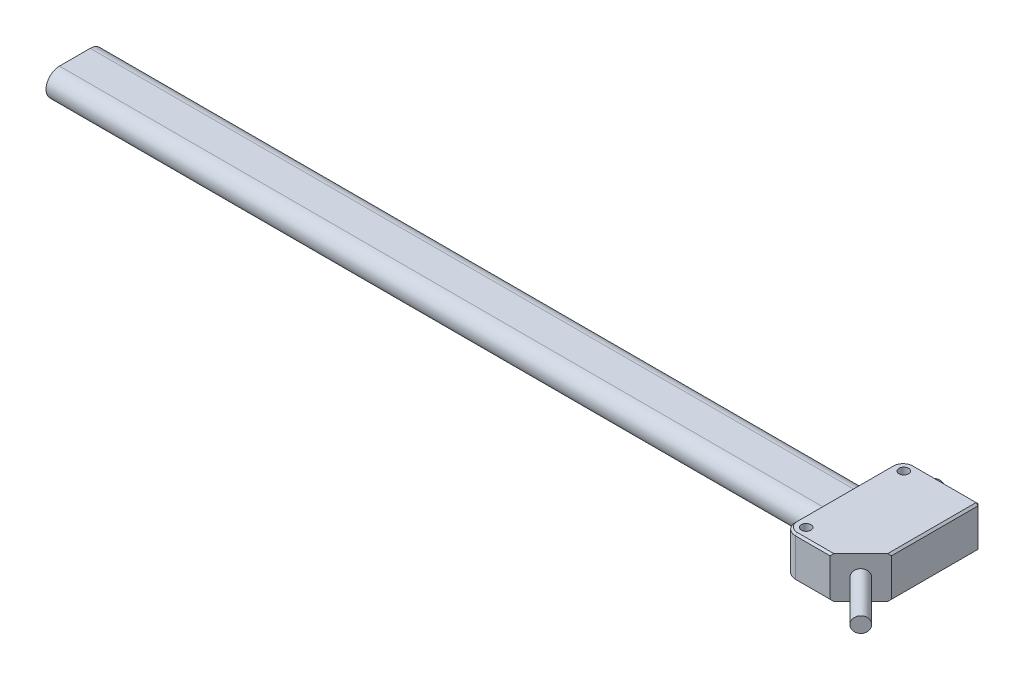
SolidWorks part; units mm, degrees
material "ABS PC"
ref_plane "前视基准面" through (0, 0, 0) normal (0, 0, 1) x (1, 0, 0)
ref_plane "上视基准面" through (0, 0, 0) normal (0, 1, 0) x (1, 0, 0)
ref_plane "右视基准面" through (0, 0, 0) normal (1, 0, 0) x (0, 0, -1)
sketch "草图1" plane through (0, 0, 0) normal (0, 1, 0) x (1, 0, 0)
  line L0 (20, -23) -> (12, -31)
  line L1 (0, 0) -> (20, 0)
  line L2 (0, 0) -> (0, -31)
  line L3 (0, -31) -> (12, -31)
  line L4 (20, 0) -> (20, -23)
  dimension "D1" = 31
  dimension "D2" = 20
  dimension "D3" = 8
  dimension "D4" = 135
extrude "凸台-拉伸1" add sketch "草图1" along normal mid plane 10.8
sketch "草图2" plane through (0, 0, 0) normal (0, 0, -1) x (-1, 0, 0)
  line L0 (-8.1, 2.3) -> (-8.1, -2.3) construction
  line L1 (-6, 2.3) -> (-6, -2.3)
  line L2 (-10.2, 2.3) -> (-10.2, -2.3)
  line L4 (0, 5.4) -> (0, -5.4) construction
  arc A0 (-6, 2.3) -> (-10.2, 2.3) centre (-8.1, 2.3) ccw
  arc A1 (-10.2, -2.3) -> (-6, -2.3) centre (-8.1, -2.3) ccw
  point P2 (-8.1, 0)
  point P11 (-8.1, 4.4)
  point P12 (-8.1, -4.4)
  dimension "D1" = 4.2
  dimension "D2" = 6
  dimension "D3" = 8.8
extrude "凸台-拉伸2" add sketch "草图2" along normal blind 2.1
fillet "圆角1" radius 2.1 4 edges at (6, 0, -2.1) (8.1, -4.4, -2.1) (10.2, 0, -2.1) (8.1, 4.4, -2.1)
sketch "草图3" plane through (0, 0, 0) normal (-1, 0, 0) x (0, 0, 1)
  line L0 (11.5, 0) -> (19.5, 0) construction
  line L1 (11.5, 3.5) -> (19.5, 3.5)
  line L2 (11.5, -3.5) -> (19.5, -3.5)
  line L3 (0, 5.4) -> (0, -5.4) construction
  arc A0 (11.5, 3.5) -> (11.5, -3.5) centre (11.5, 0) ccw
  arc A1 (19.5, -3.5) -> (19.5, 3.5) centre (19.5, 0) ccw
  point P3 (15.5, 0)
  dimension "D1" = 7
  dimension "D2" = 19.5
  dimension "D3" = 8
wrap "包覆1" sketch "草图3" wrap type scribe source sketch "草图3" face at (0, 0, 15.5)
hole_wizard "M3 螺纹孔1" positions "草图4" profile "草图5" tap size "M3" standard "GB" end condition through all
sketch "草图4" plane through (0, 5.4, 0) normal (0, 1, 0) x (1, 0, 0)
  line L0 (20, 0) -> (0, 0) construction
  line L1 (0, 0) -> (0, -31) construction
  point P0 (3, -2.8)
  point P2 (3, -28.2)
  dimension "D1" = 25.4
  dimension "D2" = 2.8
  dimension "D3" = 3
sketch "草图5" plane through (3, 5.4, 2.8) normal (1, 0, 0) x (0, 0, 1)
  line L0 (0, 0) -> (0, 10.8)
  line L1 (0, 10.8) -> (1.25, 10.8)
  line L2 (1.25, 10.8) -> (1.25, 0)
  line L5 (1.25, 0) -> (0, 0)
  line L11 (0, -6.35) -> (0, 107.95) construction
  dimension "通孔螺纹孔钻头直径" = 2.5
  dimension "通孔螺纹孔钻头深度" = 10.8
cosmetic thread "孔螺蚊线1" parameters "D2"=3
cosmetic thread "孔螺蚊线2" parameters "D2"=3
sketch "草图6" plane through (21.5, 0, 21.5) normal (0.7071, 0, 0.7071) x (0.7071, 0, -0.7071)
  line L0 (-13.435, -5.4) -> (-2.1213, 5.4) construction
  circle A0 centre (-7.7782, 0) radius 2
  dimension "D1" = 4
extrude "凸台-拉伸3" add sketch "草图6" along normal blind 15
fillet "圆角2" radius 3 2 edges at (0, 0, 31) (0, 0, 0)
chamfer "倒角1" distance 0.5 angle 45 13 edges at (7.5, -5.4, 31) (7.5, 5.4, 31) (0.8787, -5.4, 30.1213) (0.8787, 5.4, 30.1213) (0, -5.4, 15.5) (0, 5.4, 15.5) (0.8787, -5.4, 0.8787) (0.8787, 5.4, 0.8787) (20, -5.4, 11.5) (11.5, -5.4, 0) (20, 0, 0) (20, 5.4, 11.5) (11.5, 5.4, 0)
sketch "草图7" plane through (0, 0, 0) normal (-1, 0, 0) x (0, 0, 1)
  line L2 (19.5, 3.5) -> (11.5, 3.5)
  line L3 (11.5, -3.5) -> (19.5, -3.5)
  line L4 (19.5, 3.5) -> (11.5, 3.5)
  line L5 (11.5, -3.5) -> (19.5, -3.5)
  arc A2 (11.5, 3.5) -> (11.5, -3.5) centre (11.5, 0) ccw
  arc A3 (19.5, -3.5) -> (19.5, 3.5) centre (19.5, 0) ccw
  arc A4 (11.5, 3.5) -> (11.5, -3.5) centre (11.5, 0) ccw
  arc A5 (19.5, -3.5) -> (19.5, 3.5) centre (19.5, 0) ccw
  dimension "D1" = 0
extrude "凸台-拉伸4" add sketch "草图7" along normal blind 200 separate body
